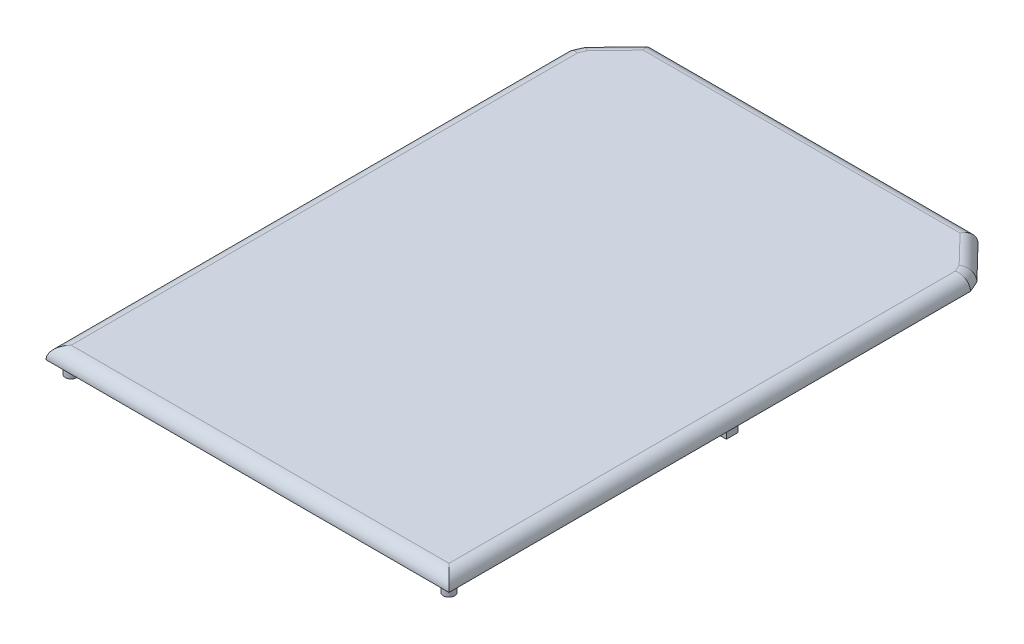
SolidWorks part; units mm, degrees
ref_plane "Front Plane" through (0, 0, 0) normal (0, 0, 1) x (1, 0, 0)
ref_plane "Top Plane" through (0, 0, 0) normal (0, 1, 0) x (1, 0, 0)
ref_plane "Right Plane" through (0, 0, 0) normal (1, 0, 0) x (0, 0, -1)
sketch "Lid" plane through (0, 0, 0) normal (0, 1, 0) x (1, 0, 0)
  line L0 (-80, -175) -> (80, -175)
  line L1 (80, -175) -> (80, 30)
  line L2 (80, 30) -> (80, 32.01)
  line L3 (78.04, 36.53) -> (65, 50)
  line L4 (65, 50) -> (-65, 50)
  line L5 (-65, 50) -> (-78.04, 36.53)
  line L6 (-78.04, 36.53) -> (-80, 32.01)
  line L7 (-80, 32.01) -> (-80, 30)
  line L8 (-80, 30) -> (-80, -175)
  line L9 (80, 32.01) -> (78.04, 36.53)
  point P0 (80, 30)
  point P1 (80, 32.01)
  point P2 (78.04, 36.53)
  point P3 (65, 50)
  point P4 (-78.04, 36.53)
  point P5 (-80, 32.01)
  point P6 (-80, 30)
  point P7 (-65, 50)
  point P8 (-80, -175)
  point P9 (80, -175)
  point P16 (0, 0)
  point P21 (0, 0)
  point P22 (0, 0)
  point P23 (0, 0)
  point P24 (0, 0)
  point P25 (0, 0)
  point P26 (0, 0)
  point P27 (0, 0)
  point P28 (0, 0)
  point P29 (0, 0)
  point P30 (0, 0)
  point P31 (0, 0)
extrude "Boss-Extrude1" add sketch "Lid" along normal blind 5 contours L1 L2 L9 L3 L4 L5 L6 L7 L8 L0
fillet "Fillet1" radius 5 8 edges at (0, 5, 175) (-79.02, 5, -34.27) (-80, 5, 71.495) (-71.52, 5, -43.265) (0, 5, -50) (71.52, 5, -43.265) (79.02, 5, -34.27) (80, 5, 71.495)
sketch "Sketch3" plane through (0, 0, 0) normal (0, 1, 0) x (1, 0, 0)
  line L0 (-77.4, -57.7) -> (-77.4, -62.3)
  line L1 (-77.4, -62.3) -> (-75.1, -62.3)
  line L2 (-75.1, -62.3) -> (-75.1, -60)
  line L3 (-75.1, -60) -> (-75.1, -57.7)
  line L4 (-75.1, -57.7) -> (-77.4, -57.7)
  line L5 (75.1, -57.7) -> (77.4, -57.7)
  line L6 (77.4, -57.7) -> (77.4, -62.3)
  line L7 (77.4, -62.3) -> (75.1, -62.3)
  line L8 (75.1, -62.3) -> (75.1, -60)
  line L9 (75.1, -60) -> (75.1, -57.7)
  circle A0 centre (-62.5, 40) radius 2.3
  circle A1 centre (62.5, 40) radius 2.3
  circle A2 centre (75, -170) radius 2.3
  circle A3 centre (-75, -170) radius 2.3
  point P0 (62.5, 40)
  point P1 (-62.5, 40)
  point P2 (-75.1, -60)
  point P3 (75.1, -60)
  point P4 (-75, -170)
  point P5 (75, -170)
  point P14 (-75.1, -57.7)
  point P15 (75.1, -57.7)
  point P16 (75.1, -62.3)
  point P17 (-75.1, -62.3)
  point P18 (-77.4, -57.7)
  point P19 (-77.4, -62.3)
  point P20 (77.4, -62.3)
  point P21 (77.4, -57.7)
  point P29 (0, 0)
  point P33 (0, 0)
  point P34 (0, 0)
  point P35 (0, 0)
  point P36 (0, 0)
  point P37 (0, 0)
  point P38 (0, 0)
  point P39 (0, 0)
  point P40 (0, 0)
  point P41 (0, 0)
  point P42 (0, 0)
  point P43 (0, 0)
  point P44 (0, 0)
  point P45 (0, 0)
  point P46 (0, 0)
  point P47 (0, 0)
  point P48 (0, 0)
  point P49 (0, 0)
extrude "Boss-Extrude2" add sketch "Sketch3" against normal blind 5
